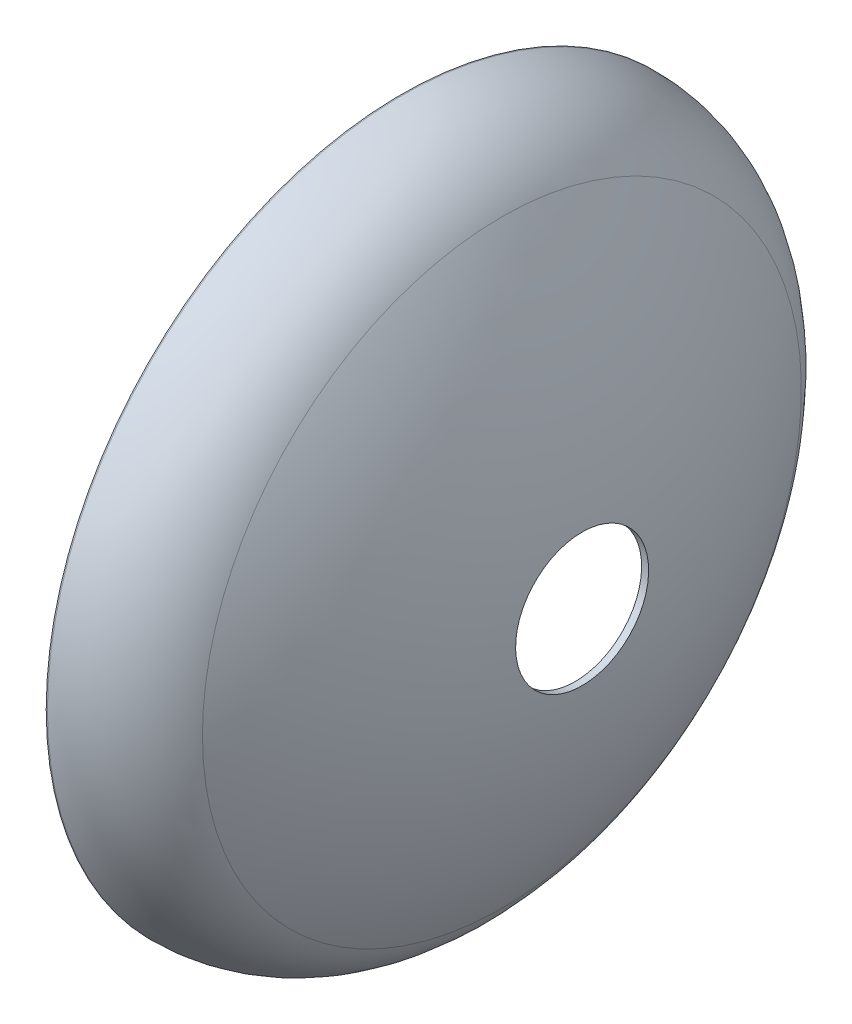
SolidWorks part; units mm, degrees
material "AISI 304"
ref_plane "Спереди" through (0, 0, 0) normal (0, 0, 1) x (1, 0, 0)
ref_plane "Сверху" through (0, 0, 0) normal (0, 1, 0) x (1, 0, 0)
ref_plane "Справа" through (0, 0, 0) normal (1, 0, 0) x (0, 0, -1)
ref_axis "Ось1" through (-62.9241, 0, 0) along (1, 0, 0)
sketch "Эскиз1" plane through (0, 0, 0) normal (0, 0, 1) x (1, 0, 0)
  line L0 (0, 0) -> (53, 0) construction
  line L1 (0, 100) -> (0, 0) construction
  line L2 (0, 102) -> (0.3488, 102)
  line L3 (0, 100) -> (0.3488, 100)
  line L4 (0, 102) -> (0, 100)
  line L5 (51, 0) -> (53, 0)
  line L6 (49.8785, 19.1) -> (51.8921, 19.1)
  arc A0 (0.3488, 102) -> (28.8538, 85.9935) centre (0.3488, 68.6154) cw
  arc A1 (28.8538, 85.9935) -> (53, 0) centre (-112.2, 0) cw
  arc A2 (0.3488, 100) -> (27.1461, 84.9524) centre (0.3488, 68.6154) cw
  arc A3 (27.1461, 84.9524) -> (51, 0) centre (-112.2, 0) cw
  point P0 (0, 101)
  dimension "D3" = 163.2
  dimension "D4" = 31.3846
  dimension "D1" = 204
  dimension "D6" = 38.2
  dimension "D5" = 53
  dimension "D2" = 2
revolve "Повернуть1" add sketch "Эскиз1" angle 360 about L0 region at (0.1744, 101.022, 0)
ref_plane "Плоскость1" through (53, 0, 0) normal (1, 0, 0) x (0, 0, -1)
equation "\"D\"= 204мм"
equation "\"D1@Эскиз1\"=\"D\""
equation "\"D3@Эскиз1\"=\"D\"*0.8"
equation "\"D4@Эскиз1\"=\"D\"/6.5"
